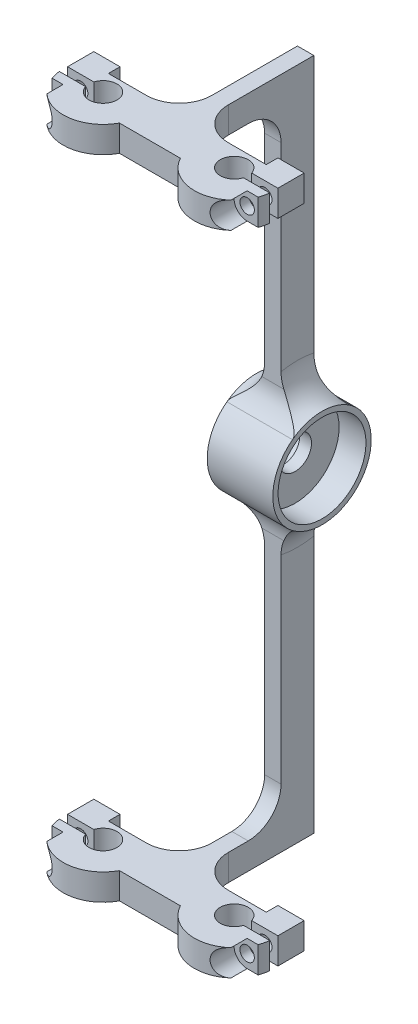
SolidWorks part; units mm, degrees
material "PLA Black"
ref_plane "Front" through (0, 0, 0) normal (0, 0, 1) x (1, 0, 0)
ref_plane "Top" through (0, 0, 0) normal (0, 1, 0) x (1, 0, 0)
ref_plane "Right" through (0, 0, 0) normal (1, 0, 0) x (0, 0, -1)
sketch "Sketch1" plane through (0, 0, 0) normal (1, 0, 0) x (0, 0, -1)
  line L0 (0, 100.9459) -> (0, -99.0541) construction
  line L1 (-11.4058, 102.6846) -> (-11.4058, 94.6846)
  line L2 (-11.4058, 94.6846) -> (26.0619, 94.6846)
  line L3 (-11.4058, 102.6846) -> (36.0619, 102.6846)
  line L4 (-19.0433, 0) -> (30.354, 0) construction
  line L5 (-11.4058, -102.6846) -> (36.0619, -102.6846)
  line L6 (-11.4058, -94.6846) -> (26.0619, -94.6846)
  line L7 (-11.4058, -102.6846) -> (-11.4058, -94.6846)
  line L8 (36.0619, 102.6846) -> (36.0619, -13.4401)
  line L9 (26.0619, 94.6846) -> (26.0619, -94.6846)
  line L10 (36.0619, -13.4401) -> (36.0619, -102.6846)
  dimension "D1" = 200
  dimension "D2" = 8
  dimension "D3" = 10
extrude "Boss-Extrude1" add sketch "Sketch1" along normal mid plane 5
sketch "Sketch2" plane through (0, 102.6846, -93.2787) normal (0, -1, 0) x (1, 0, 0)
  line L0 (-24.062, 93.2787) -> (24.062, 93.2787)
  line L1 (24.062, 93.2787) -> (24.062, 89.7316)
  line L2 (24.062, 89.7316) -> (32.062, 89.7316)
  line L3 (24.062, 97.7316) -> (24.062, 85.5924) construction
  line L4 (32.062, 89.7316) -> (32.062, 97.7316)
  line L5 (0, 80.7776) -> (0, 113.4638) construction
  line L6 (-9.2981, 104.6846) -> (9.2981, 104.6846)
  line L7 (32.062, 97.7316) -> (24.062, 97.7316)
  line L8 (24.062, 100.2316) -> (32.062, 100.2316)
  line L9 (-24.062, 100.2316) -> (-32.062, 100.2316)
  line L10 (-32.062, 97.7316) -> (-24.062, 97.7316)
  line L11 (-24.062, 89.7316) -> (-32.062, 89.7316)
  line L12 (-32.062, 89.7316) -> (-32.062, 97.7316)
  line L13 (-24.062, 89.7316) -> (-24.062, 93.2787)
  line L14 (-2.5, 104.6846) -> (21.1341, 104.6846) construction
  line L15 (20, 104.6846) -> (20, 93.2787) construction
  arc A0 (32.062, 100.2316) -> (9.2981, 104.6846) centre (20, 98.9816) ccw
  arc A1 (-32.062, 100.2316) -> (-9.2981, 104.6846) centre (-20, 98.9816) cw
  arc A2 (24.062, 100.2316) -> (24.062, 97.7316) centre (20, 98.9816) ccw
  arc A3 (-24.062, 100.2316) -> (-24.062, 97.7316) centre (-20, 98.9816) cw
  arc A4 (-24.062, 100.2316) -> (-24.062, 97.7316) centre (-20, 98.9816) cw
  line M5 (-2.5, 57.2168) -> (-2.5, 104.6846)
  line M7 (2.5, 104.6846) -> (2.5, 57.2168)
  dimension "D2" = 2.5
  dimension "D3" = 8.5
  dimension "D4" = 8
  dimension "D1" = 40
  dimension "D5" = 8
extrude "Boss-Extrude2" add sketch "Sketch2" along normal blind 8 contours A3 L9 A1 L6 L0 L13 L11 L12 L10 M5 | L8 A2 L7 L4 L2 L1 L0 L6 A0 M7 region at (-24.4268, 102.6846, -1.7735) region at (2.8648, 102.6846, 5.7029)
sketch "Sketch7" plane through (0, 0, -3.5471) normal (0, 0, -1) x (-1, 0, 0)
  line L0 (-28.062, 102.6846) -> (-28.062, 94.6846) construction
  line L1 (-24.062, 102.6846) -> (-32.062, 102.6846) construction
  line L3 (-32.062, 98.6846) -> (-24.062, 98.6846) construction
  line L4 (-32.062, 94.6846) -> (-32.062, 102.6846) construction
  line L5 (-24.062, 94.6846) -> (-24.062, 102.6846) construction
  line L6 (0, 111.5451) -> (0, 86.699) construction
  line L7 (-24.062, 94.6846) -> (-32.062, 94.6846) construction
  circle A0 centre (-28.062, 98.6846) radius 2.2
  circle A1 centre (28.062, 98.6846) radius 2.2
  dimension "D1" = 4.4
extrude "Cut-Extrude3" cut sketch "Sketch7" against normal through all
ref_plane "Plane1" through (0, 0, 17.8295) normal (0, 0, 1) x (1, 0, 0)
sketch "Sketch8" plane through (0, 0, 17.8295) normal (0, 0, 1) x (1, 0, 0)
  line L1 (0, 111.4996) -> (0, 91.8899) construction
  line L2 (28.062, 102.6846) -> (32.062, 102.6846)
  line L3 (32.062, 102.6846) -> (32.062, 94.6846)
  line L4 (32.062, 94.6846) -> (28.062, 94.6846)
  line L5 (24.062, 102.6846) -> (32.062, 102.6846) construction
  line L6 (-32.062, 94.6846) -> (-28.062, 94.6846)
  line L7 (-32.062, 102.6846) -> (-32.062, 94.6846)
  line L8 (-28.062, 102.6846) -> (-32.062, 102.6846)
  arc A0 (28.062, 102.6846) -> (28.062, 94.6846) centre (28.062, 98.6846) ccw
  arc A1 (-28.062, 102.6846) -> (-28.062, 94.6846) centre (-28.062, 98.6846) cw
extrude "Cut-Extrude4" cut sketch "Sketch8" against normal blind 8
mirror "Mirror4" about plane through (0, 0, 0) normal (0, 1, 0) of "Boss-Extrude2", "Cut-Extrude3", "Cut-Extrude4"
sketch "Sketch4" plane through (0, 0, 0) normal (1, 0, 0) x (0, 0, -1)
  line L0 (31.0619, 6.4033) -> (31.0619, -4.3005) construction
  line L2 (26.0619, 94.6846) -> (26.0619, -94.6846) construction
  line L3 (36.0619, -102.6846) -> (36.0619, 102.6846) construction
  circle A0 centre (31.0619, 0) radius 15
  dimension "D1" = 30
extrude "Boss-Extrude4" add sketch "Sketch4" along normal mid plane 20 contours A0
sketch "Sketch5" plane through (10, 0, 0) normal (1, 0, 0) x (0, 0, -1)
  circle A0 centre (31.0619, 0) radius 13.4
  circle A1 centre (31.0619, 0) radius 15 construction
  dimension "D1" = 26.8
extrude "Cut-Extrude1" cut sketch "Sketch5" against normal blind 8.2
mirror "Mirror3" about plane through (0, 0, 0) normal (1, 0, 0) of "Cut-Extrude1"
sketch "Sketch6" plane through (1.8, 0, 0) normal (1, 0, 0) x (0, 0, -1)
  circle A0 centre (31.0619, 0) radius 5
  circle A1 centre (31.0619, 0) radius 13.4 construction
  dimension "D1" = 10
extrude "Cut-Extrude2" cut sketch "Sketch6" against normal through all contours A0
fillet "Fillet1" radius 10 14 edges at (0, -94.6846, -26.0619) (0, 94.6846, -26.0619) (2.5, -15, -31.0619) (0, -14.1421, -36.0619) (-2.5, -15, -31.0619) (0, -14.1421, -26.0619) (0, 14.1421, -26.0619) (-2.5, 15, -31.0619) (0, 14.1421, -36.0619) (2.5, 15, -31.0619) (2.5, -98.6846, 0) (-2.5, -98.6846, 0)
